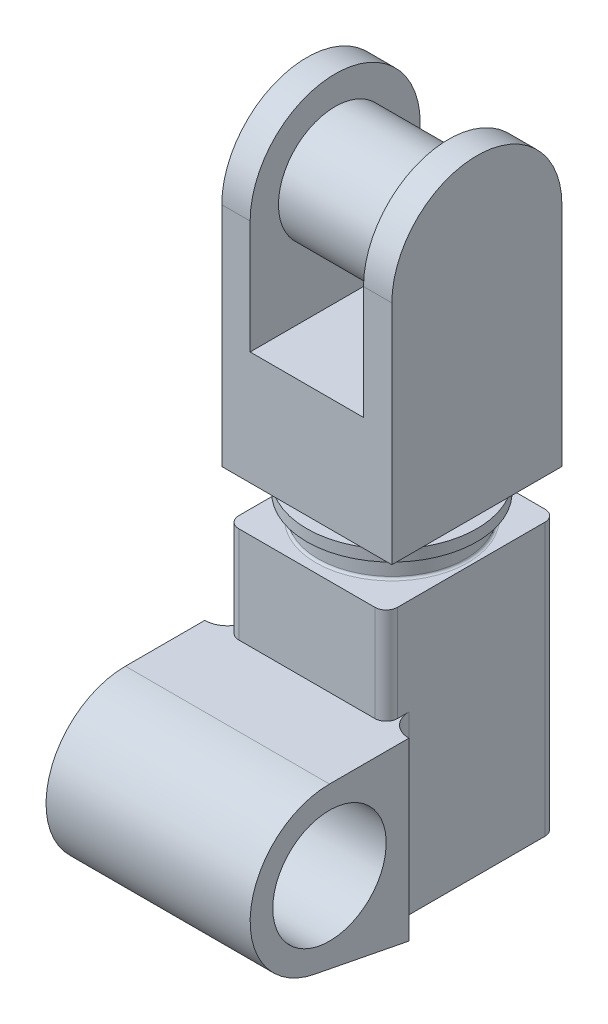
SolidWorks part; units mm, degrees
ref_plane "Front Plane" through (0, 0, 0) normal (0, 0, 1) x (1, 0, 0)
ref_plane "Top Plane" through (0, 0, 0) normal (0, 1, 0) x (1, 0, 0)
ref_plane "Right Plane" through (0, 0, 0) normal (1, 0, 0) x (0, 0, -1)
sketch "Sketch1" plane through (0, 0, 0) normal (0, 1, 0) x (1, 0, 0)
  line L1 (70, -75) -> (-70, -75)
  line L2 (70, -75) -> (70, 75)
  line L3 (70, 75) -> (-70, 75)
  line L4 (-70, -75) -> (-70, 75)
  line L5 (70, -75) -> (-70, 75) construction
  line L6 (70, 75) -> (-70, -75) construction
  point P0 (0, 0)
  dimension "D1" = 150
  dimension "D2" = 140
extrude "Boss-Extrude1" add sketch "Sketch1" along normal blind 240
sketch "Sketch2" plane through (0, 240, 0) normal (0, 1, 0) x (1, 0, 0)
  circle A0 centre (0, 0) radius 65
  dimension "D1" = 130
extrude "Boss-Extrude2" add sketch "Sketch2" along normal blind 20
sketch "Sketch3" plane through (0, 260, 0) normal (0, 1, 0) x (1, 0, 0)
  circle A2 centre (0, 0) radius 75
  circle A3 centre (0, 0) radius 75
  dimension "D1" = 10
extrude "Boss-Extrude3" add sketch "Sketch3" along normal blind 10
sketch "Sketch4" plane through (0, 270, 0) normal (0, 1, 0) x (1, 0, 0)
  circle A0 centre (0, 0) radius 40
  dimension "D1" = 80
extrude "Cut-Extrude2" cut sketch "Sketch4" against normal blind 50
sketch "Sketch5" plane through (0, 0, 0) normal (1, 0, 0) x (0, 0, -1)
  line L0 (-145, 155) -> (-75, 155)
  line L1 (-75, 240) -> (-75, 0) construction
  line L2 (-75, 0) -> (75, 0) construction
  line L3 (-75, 0) -> (-158.4213, 16.3061)
  line L4 (-75, 155) -> (-75, 0)
  circle A0 centre (-145, 85) radius 50
  arc A1 (-145, 155) -> (-157.4351, 16.1134) centre (-145, 85) ccw
  dimension "D1" = 100
  dimension "D2" = 140
  dimension "D3" = 70
  dimension "D4" = 155
  dimension "D5" = 85
  dimension "D6" = 191.06
extrude "Boss-Extrude4" add sketch "Sketch5" along normal mid plane 180 contours L0 A1 L3 L4 A0 region at (0, 152.9113, 110)
fillet "Fillet1" radius 2 1 edges at (0, 240, 65)
fillet "Fillet2" radius 20 2 edges at (-70, 77.5, 75) (70, 77.5, 75)
fillet "Fillet3" radius 10 4 edges at (-70, 197.5, 75) (-70, 120, -75) (70, 120, -75) (70, 197.5, 75)
sketch "Sketch6" plane through (0, 270, 0) normal (0, 1, 0) x (1, 0, 0)
  circle A0 centre (0, 0) radius 65
  dimension "D1" = 130
extrude "Boss-Extrude5" add sketch "Sketch6" along normal blind 10
sketch "Sketch7" plane through (0, 0, 0) normal (1, 0, 0) x (0, 0, -1)
  line L4 (-75, 280) -> (75, 280)
  line L5 (75, 270) -> (-75, 270) construction
  line L6 (75, 280) -> (75, 480)
  line L7 (-75, 280) -> (-75, 480)
  arc A0 (75, 480) -> (-75, 480) centre (0, 480) ccw
  dimension "D2" = 150
  dimension "D3" = 10
  dimension "D1" = 150
  dimension "D4" = 200
extrude "Boss-Extrude6" add sketch "Sketch7" along normal mid plane 150 contours L7 A0 L6 L4
sketch "Sketch8" plane through (0, 0, 0) normal (1, 0, 0) x (0, 0, -1)
  line L0 (75, 480) -> (75, 380)
  line L1 (75, 280) -> (75, 480) construction
  line L2 (75, 380) -> (-75, 380)
  line L3 (-75, 280) -> (-75, 480) construction
  line L4 (-75, 380) -> (-75, 480)
  arc A0 (75, 480) -> (-75, 480) centre (0, 480) ccw
extrude "Cut-Extrude3" cut sketch "Sketch8" against normal mid plane 100
sketch "Sketch9" plane through (50, 0, 0) normal (-1, 0, 0) x (0, 0, 1)
  circle A0 centre (0, 480) radius 50
  dimension "D1" = 100
extrude "Boss-Extrude7" add sketch "Sketch9" along normal blind 100
fillet "Fillet4" radius 2 1 edges at (0, 280, 65)
sketch "Sketch14" plane through (0, 0, -75) normal (0, 0, -1) x (-1, 0, 0)
  line L2 (-15, 239) -> (-15, 189)
  line L4 (15, 239) -> (15, 189)
  line L5 (0, 145.0012) -> (0, -145.0012) construction
  line L8 (15, 239) -> (-15, 239)
  line L9 (-60, 240) -> (60, 240) construction
  arc A0 (-15, 189) -> (15, 189) centre (0, 189) ccw
  dimension "D3" = 15
  dimension "D1" = 50
  dimension "D2" = 30
  dimension "D4" = 1
extrude "Cut-Extrude5" cut sketch "Sketch14" against normal blind 2
sketch "Sketch15" plane through (0, 0, 0) normal (1, 0, 0) x (0, 0, -1)
  point P0 (-145, 85)
move or copy body "Body-Move/Copy1" bodies to move or copy 114 copy no translate (0, -85, -145)
